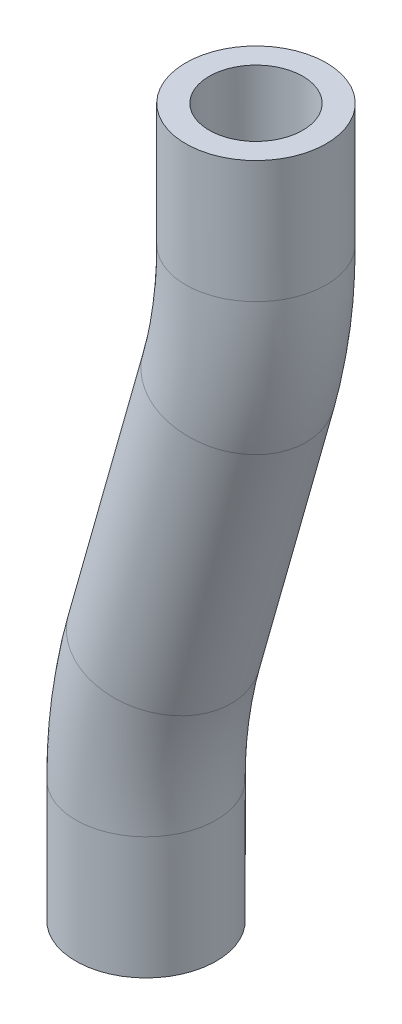
SolidWorks part; units mm, degrees
material "PE High Density"
ref_plane "Front Plane" through (0, 0, 0) normal (0, 0, 1) x (1, 0, 0)
ref_plane "Top Plane" through (0, 0, 0) normal (0, 1, 0) x (1, 0, 0)
ref_plane "Right Plane" through (0, 0, 0) normal (1, 0, 0) x (0, 0, -1)
sketch "Sketch1" plane through (0, 0, 0) normal (0, 0, 1) x (1, 0, 0)
  line L0 (0, 0) -> (0, 5.2233)
  line L1 (0.7565, 10.6717) -> (3.9435, 21.9283)
  line L2 (4.7, 27.3767) -> (4.7, 32.6)
  arc A0 (0, 5.2233) -> (0.7565, 10.6717) centre (20, 5.2233) cw
  arc A1 (3.9435, 21.9283) -> (4.7, 27.3767) centre (-15.3, 27.3767) ccw
  point P8 (0, 8)
  point P11 (4.7, 24.6)
  dimension "D4" = 20
  dimension "D1" = 32.6
  dimension "D2" = 4.7
  dimension "D3" = 8
sweep "Sweep-Thin1" add path "Sketch1" circular profile diameter 6 parameters "D1"=1, "D3"=6
